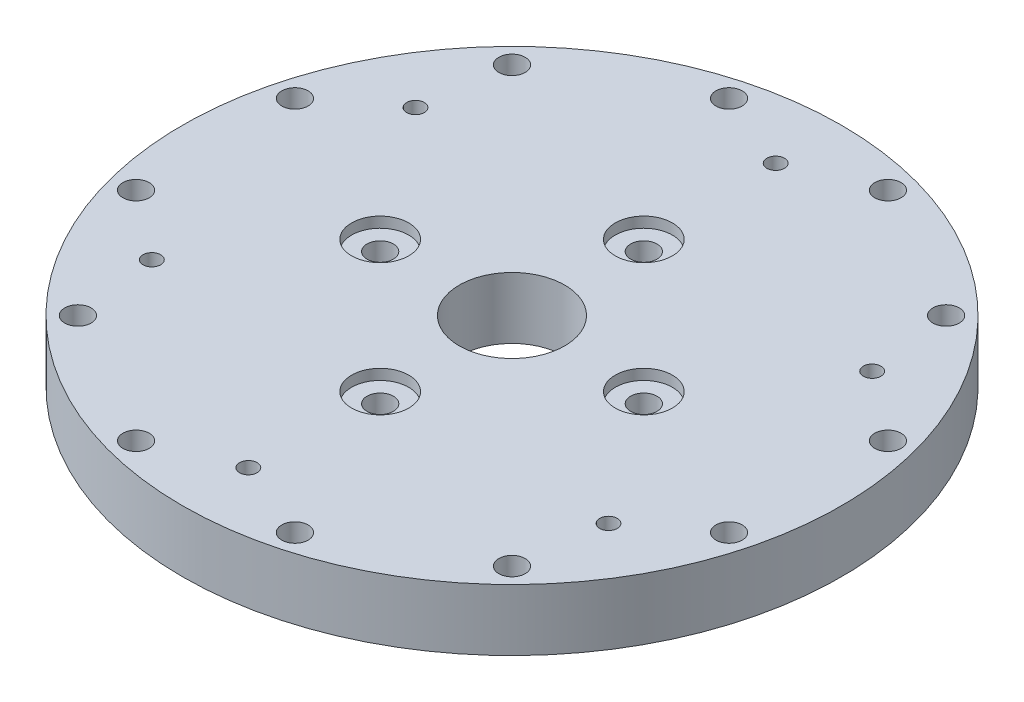
SolidWorks part; units mm, degrees
ref_plane "Front Plane" through (0, 0, 0) normal (0, 0, 1) x (1, 0, 0)
ref_plane "Top Plane" through (0, 0, 0) normal (0, 1, 0) x (1, 0, 0)
ref_plane "Right Plane" through (0, 0, 0) normal (1, 0, 0) x (0, 0, -1)
sketch "Sketch1" plane through (0, 0, 0) normal (0, 1, 0) x (1, 0, 0)
  line L0 (-49.4318, 0) -> (0, 0) construction
  line L1 (0, 0) -> (-47.2333, -12.6561) construction
  circle A0 centre (0, 0) radius 37.5
  circle A1 centre (0, 0) radius 30 construction
  circle A2 centre (0, 0) radius 6
  circle A3 centre (0, 0) radius 15 construction
  circle A4 centre (0, 15) radius 1.5
  circle A5 centre (15, 0) radius 1.5
  circle A6 centre (0, -15) radius 1.5
  circle A7 centre (-15, 0) radius 1.5
  circle A11 centre (0, 0) radius 35 construction
  circle A12 centre (-33.737, -9.0398) radius 1.5
  circle A13 centre (-33.737, 9.0398) radius 1.5
  circle A14 centre (-24.6972, 24.6972) radius 1.5
  circle A15 centre (-9.0398, 33.737) radius 1.5
  circle A16 centre (9.0398, 33.737) radius 1.5
  circle A17 centre (24.6972, 24.6972) radius 1.5
  circle A18 centre (33.737, 9.0398) radius 1.5
  circle A19 centre (33.737, -9.0398) radius 1.5
  circle A20 centre (24.6972, -24.6972) radius 1.5
  circle A21 centre (9.0398, -33.737) radius 1.5
  circle A22 centre (-9.0398, -33.737) radius 1.5
  circle A23 centre (-24.6972, -24.6972) radius 1.5
  circle A24 centre (0, 30) radius 1
  circle A25 centre (25.9808, 15) radius 1
  circle A26 centre (25.9808, -15) radius 1
  circle A27 centre (0, -30) radius 1
  circle A28 centre (-25.9808, -15) radius 1
  circle A29 centre (-25.9808, 15) radius 1
  point P17 (0, 0)
  point P44 (0, 0)
  point P57 (0, 0)
  dimension "D1" = 75
  dimension "D2" = 60
  dimension "D3" = 12
  dimension "D4" = 3
  dimension "D6" = 30
  dimension "D7" = 70
  dimension "D9" = 3
  dimension "D11" = 2
  dimension "D8" = 15
  dimension "D5" = 4
  dimension "D10" = 12
  dimension "D12" = 6
extrude "Boss-Extrude1" add sketch "Sketch1" along normal blind 7
sketch "Sketch2" plane through (0, 7, 0) normal (0, 1, 0) x (1, 0, 0)
  circle A0 centre (0, 0) radius 15 construction
  circle A1 centre (0, 15) radius 3.25
  circle A2 centre (15, 0) radius 3.25
  circle A3 centre (0, -15) radius 3.25
  circle A4 centre (-15, 0) radius 3.25
  point P15 (0, 0)
  dimension "D1" = 6.5
  dimension "D2" = 4
extrude "Cut-Extrude1" cut sketch "Sketch2" against normal blind 1.2
